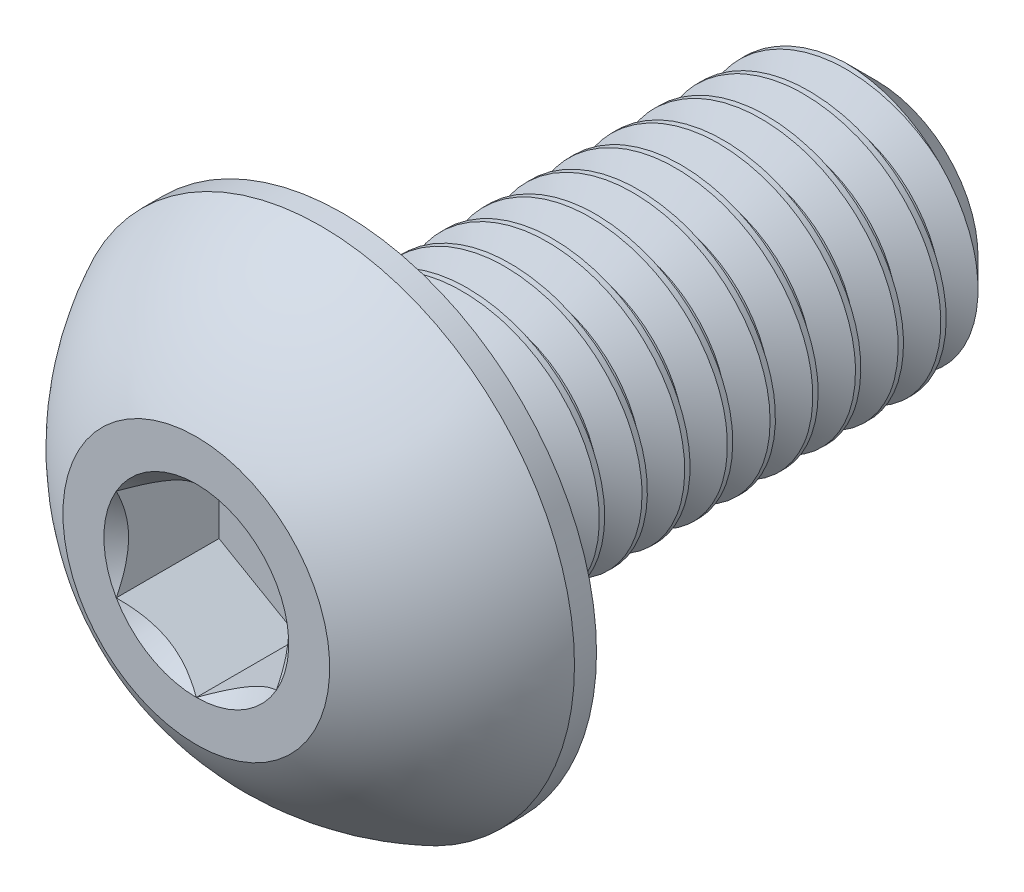
SolidWorks part; units mm, degrees
note: '?' marks a value the reader was unsure of.
ref_plane "Front" through (0, 0, 0) normal (0, 0, 1) x (1, 0, 0)
ref_plane "Top" through (0, 0, 0) normal (0, 1, 0) x (1, 0, 0)
ref_plane "Right" through (0, 0, 0) normal (1, 0, 0) x (0, 0, -1)
sketch "Sketch1" plane through (0, 0, 0) normal (1, 0, 0) x (0, 0, -1)
  line L2 (2.75, 2.5) -> (12.75, 2.5)
  line L3 (12.75, 2.5) -> (12.75, 0)
  line L4 (12.75, 0) -> (2.75, 0)
  line L6 (2.3375, 4.75) -> (2.75, 4.75) construction
  line L7 (12.75, 2.5) -> (12.75, -2.5) construction
  line L8 (0, 0) -> (2.75, 0) construction
  line L9 (2.75, 4.75) -> (2.75, -4.75) construction
  line L11 (2.75, 2.5) -> (2.75, 0)
  line L13 (0, 1.5) -> (0, -1.5) construction
  line L14 (0, 1.5) -> (0, 2.5) construction
  arc A3 (0, 2.5) -> (2.3375, 4.75) centre (4.6581, 0) cw construction
  dimension "D1" = 0.4125
revolve "Revolve1" add sketch "Sketch1" angle 360 mid plane about L4
sketch "Sketch3" plane through (0, 0, -12.75) normal (0, 0, -1) x (-1, 0, 0)
  circle A0 centre (0, 0) radius 2.5
curve "Helix/Spiral1" pitch 0.8 height 10.8 turns 13.5
chamfer "Chamfer1" distance 0.6 angle 45 1 edges at (0, 2.5, -12.75)
sketch "Sketch7" plane through (0, 0, 0) normal (1, 0, 0) x (0, 0, -1)
  line L6 (2.3375, 4.75) -> (2.75, 4.75) construction
  line L8 (0, 0) -> (2.75, 0) construction
  line L11 (2.75, 4.75) -> (2.75, -4.75) construction
  line L12 (2.3375, 4.75) -> (2.75, 4.75)
  line L13 (0, 0) -> (2.75, 0)
  line L14 (0, 1.5) -> (0, -1.5) construction
  line L15 (2.75, 4.75) -> (2.75, 0)
  line L16 (0, 2.5) -> (0, 0)
  arc A2 (2.3375, 4.75) -> (0, 2.5) centre (4.6581, 0) ccw construction
  arc A3 (2.3375, 4.75) -> (0, 2.5) centre (4.6581, 0) ccw
revolve "Revolve2" add sketch "Sketch7" angle 360 mid plane about L13
sketch "Sketch5" plane through (0, 0, 0) normal (0, 0, 1) x (1, 0, 0)
  line L1 (1.5, -0.866) -> (1.5, 0.866)
  line L2 (1.5, 0.866) -> (0, 1.7321)
  line L3 (0, 1.7321) -> (-1.5, 0.866)
  line L4 (-1.5, 0.866) -> (-1.5, -0.866)
  line L5 (-1.5, -0.866) -> (0, -1.7321)
  line L6 (0, -1.7321) -> (1.5, -0.866)
  circle A0 centre (0, 0) radius 1.5 construction
extrude "Cut-Extrude2" cut sketch "Sketch5" against normal blind 1.925
sketch "Sketch6" plane through (0, 0, 0) normal (0, 0, 1) x (1, 0, 0)
  circle A0 centre (0, 0) radius 1.7321
extrude "Cut-Extrude3" cut sketch "Sketch6" against normal blind 1.925 draft 45
sketch "Sketch2" plane through (0, 0, 0) normal (1, 0, 0) x (0, 0, -1)
  line L0 (12.15, 2.5) -> (12.85, 2.5)
  line L1 (12.85, 2.5) -> (12.55, 1.9804)
  line L2 (12.55, 1.9804) -> (12.45, 1.9804)
  line L3 (12.45, 1.9804) -> (12.15, 2.5)
  line L4 (12.3, 2.2402) -> (12.7, 2.2402) construction
  dimension "D1" = 60
  dimension "D2" = 0.1
  dimension "D3" = 0.4
sweep "Cut-Sweep1" cut profiles "Sketch2" path "Helix/Spiral1"
sketch "Sketch10" plane through (0, 0, 0) normal (1, 0, 0) x (0, 0, -1)
  line L0 (12.75, 2.5) -> (12.75, -2.5) construction
  point P0 (11.55, -2.5)
  dimension "D1" = 1.2
ref_axis "Center Axis 1" through (0, 0, -8.1113) along (0, 0, 1)?
ref_plane "Contact Plane 1" through (0, 0, -2.75) normal (0, 0, -1) x (-1, 0, 0)
ref_plane "Contact Plane 2" through (0, 0, 0) normal (0, 0, 1) x (1, 0, 0)
equation "\"D3@Helix/Spiral1\" = \"Lg@Sketch1\" + \"D4@Helix/Spiral1\""
equation "\"D2@Sketch2\" = \"D4@Helix/Spiral1\" * .125"
equation "\"D3@Sketch2\" = \"D4@Helix/Spiral1\" * .5"
equation "\"D1@Chamfer1\" = \"D4@Helix/Spiral1\" * .75"
equation "\"D1@Cut-Extrude2\" = \"Head Ht@Sketch1\" * .7"
equation "\"D1@Sketch1\" = \"Head Ht@Sketch1\" * .15"
equation "\"D1@Sketch10\" = \"D4@Helix/Spiral1\" * 1.5"
equation "\"D1@Cut-Extrude3\" = \"D1@Cut-Extrude2\""
